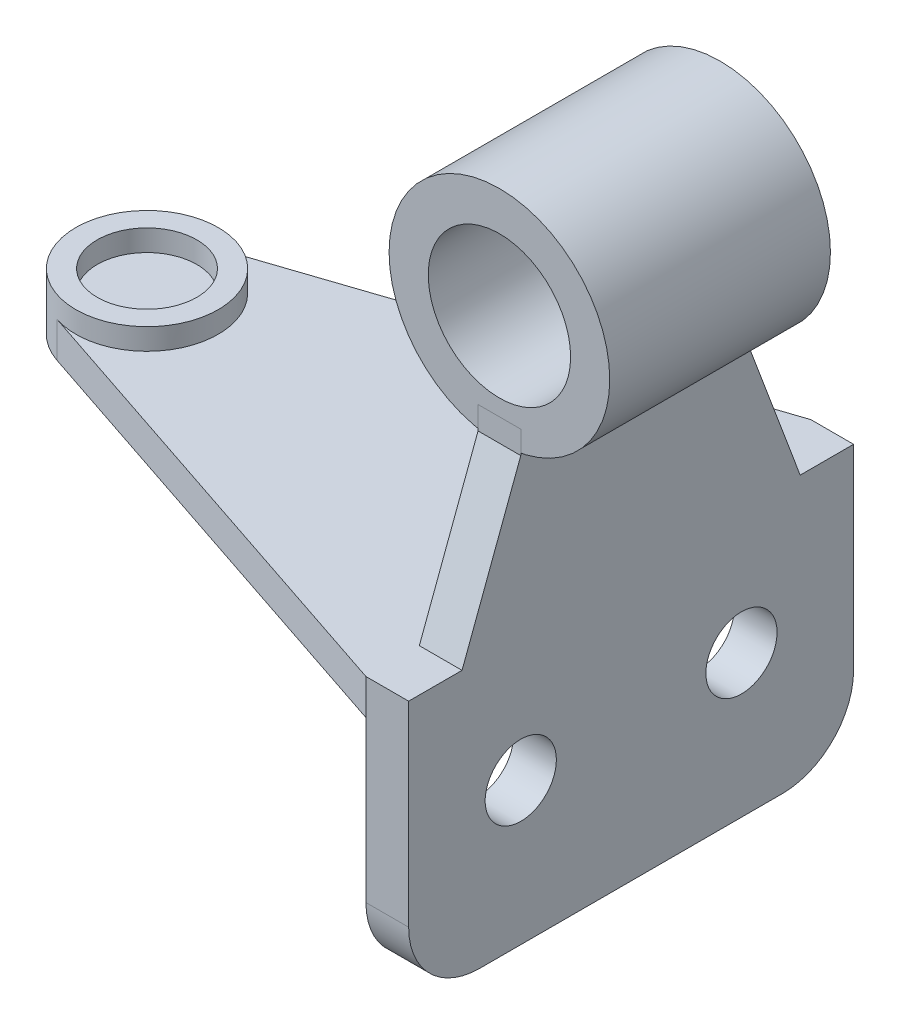
SolidWorks part; units mm, degrees
ref_plane "Front Plane" through (0, 0, 0) normal (0, 0, 1) x (1, 0, 0)
ref_plane "Top Plane" through (0, 0, 0) normal (0, 1, 0) x (1, 0, 0)
ref_plane "Right Plane" through (0, 0, 0) normal (1, 0, 0) x (0, 0, -1)
sketch "Sketch2" plane through (0, 0, 0) normal (0, 1, 0) x (1, 0, 0)
  line L0 (-136, 0) -> (2.238, 0) construction
  line L1 (0, 0) -> (0, 62.5)
  line L2 (0, 0) -> (0, -62.5)
  line L3 (0, -62.5) -> (-12, -62.5)
  line L4 (-12, -62.5) -> (-142.3357, -18.97)
  line L5 (-12, 62.5) -> (-142.3357, 18.97)
  line L6 (0, 62.5) -> (-12, 62.5)
  arc A0 (-142.3357, 18.97) -> (-142.3357, -18.97) centre (-136, 0) ccw
extrude "Boss-Extrude1" add sketch "Sketch2" along normal blind 10
sketch "Sketch3" plane through (0, 10, 0) normal (0, 1, 0) x (1, 0, 0)
  circle A1 centre (-136, 0) radius 20
  arc A2 (-142.3357, 18.97) -> (-142.3357, -18.97) centre (-136, 0) ccw construction
  circle A3 centre (-136, 0) radius 14
  dimension "D1" = 28
extrude "Boss-Extrude3" add sketch "Sketch3" along normal blind 6
sketch "Sketch7" plane through (0, 0, 0) normal (0, 0, 1) x (1, 0, 0)
  line L0 (-6, 118.1158) -> (-6, -40.1478) construction
  line L1 (0, 10) -> (0, 0) construction
  line L2 (-142.3357, 10) -> (-12, 10) construction
  circle A2 centre (-6, 85) radius 31
  circle A3 centre (-6, 85) radius 20
  dimension "D2" = 62
  dimension "D3" = 40
  dimension "D1" = 6
  dimension "D4" = 75
extrude "Boss-Extrude4" add sketch "Sketch7" along normal blind 31 and the other way blind 31 separate body
sketch "Sketch8" plane through (0, 0, 0) normal (1, 0, 0) x (0, 0, -1)
  line L0 (-47.5, 10) -> (-31, 54)
  line L1 (-62.5, 10) -> (62.5, 10) construction
  line L2 (31, 54) -> (47.5, 10)
  line L3 (0, 0) -> (0, -31.8647) construction
  line L4 (-47.5, 10) -> (47.5, 10)
  line L6 (-31, 54) -> (31, 54) construction
  line L7 (-31, 54) -> (-31, 60.431)
  line L8 (-31, 116) -> (-31, 54) construction
  line L9 (31, 54) -> (31, 60.431)
  line L10 (31, 60.431) -> (-31, 60.431)
  dimension "D1" = 95
extrude "Boss-Extrude5" add sketch "Sketch8" against normal blind 12
sketch "Sketch9" plane through (0, 0, 0) normal (1, 0, 0) x (0, 0, -1)
  line L0 (-62.5, 0) -> (62.5, 0)
  line L1 (62.5, 0) -> (62.5, -45)
  line L2 (42.5, -65) -> (-42.5, -65)
  line L3 (-62.5, -45) -> (-62.5, 0)
  line L4 (-62.5, 10) -> (-47.5, 10) construction
  arc A0 (-62.5, -45) -> (-42.5, -65) centre (-42.5, -45) ccw
  arc A1 (42.5, -65) -> (62.5, -45) centre (42.5, -45) ccw
  dimension "D1" = 20
  dimension "D2" = 20
  dimension "D3" = 75
extrude "Boss-Extrude6" add sketch "Sketch9" against normal blind 12
sketch "Sketch10" plane through (0, 0, 0) normal (1, 0, 0) x (0, 0, -1)
  line L0 (0, 0) -> (0, -50.3644) construction
  line L1 (-62.5, 10) -> (-47.5, 10) construction
  circle A0 centre (-31, -25) radius 10
  circle A1 centre (31, -25) radius 10
  dimension "D1" = 35
  dimension "D3" = 20
  dimension "D2" = 62
extrude "Boss-Extrude7" add sketch "Sketch10" against normal blind 12
extrude "Cut-Extrude2" cut sketch "Sketch10<4>" against normal blind 12
sketch "Sketch10<4>" plane through (0, 0, 0) normal (1, 0, 0) x (0, 0, -1) same geometry as "Sketch10"
sketch "Sketch11" plane through (0, 0, 0) normal (0, 0, 1) x (1, 0, 0)
  line L0 (0, -25) -> (24.1351, 77.7285)
  line L1 (0, 10) -> (0, -45) construction
  line L2 (0, -25) -> (0, 54.5862)
  line L3 (-142.3357, 10) -> (-12, 10) construction
  circle A0 centre (-6, 85) radius 31 construction
  circle A1 centre (-6, 85) radius 31
  circle A3 centre (-6, 85) radius 31
  circle A4 centre (-6, 85) radius 31
  dimension "D1" = 35
  dimension "D2" = 0
ref_plane "Plane1" through (0, 10, 47.5) normal (0, -0.9363, 0.3511) x (-1, 0, 0)
